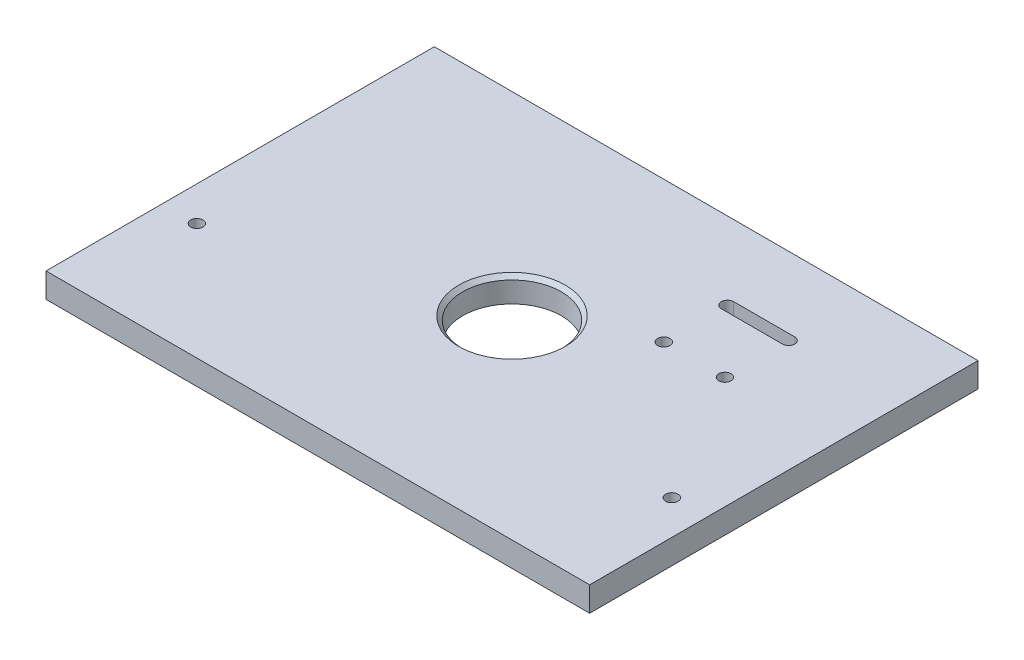
SolidWorks part; units mm, degrees
material "Oak"
ref_plane "Front Plane" through (0, 0, 0) normal (0, 0, 1) x (1, 0, 0)
ref_plane "Top Plane" through (0, 0, 0) normal (0, 1, 0) x (1, 0, 0)
ref_plane "Right Plane" through (0, 0, 0) normal (1, 0, 0) x (0, 0, -1)
sketch "Sketch1" plane through (0, 0, 0) normal (0, 1, 0) x (1, 0, 0)
  line L1 (0, 0) -> (140, 0)
  line L2 (0, 0) -> (0, 100)
  line L3 (0, 100) -> (140, 100)
  line L4 (140, 0) -> (140, 100)
  dimension "D1" = 140
  dimension "D2" = 100
extrude "Boss-Extrude1" add sketch "Sketch1" along normal blind 6.35
sketch "Sketch2" plane through (0, 6.35, 0) normal (0, 1, 0) x (1, 0, 0)
  line L0 (70, 100) -> (70, 0) construction
  line L1 (140, 100) -> (0, 100) construction
  line L2 (0, 0) -> (140, 0) construction
  line L3 (0, 50) -> (140, 50) construction
  line L4 (0, 100) -> (0, 0) construction
  line L5 (140, 0) -> (140, 100) construction
  circle A0 centre (70, 50) radius 12.705
  dimension "D1" = 25.41
extrude "Cut-Extrude1" cut sketch "Sketch2" against normal blind 10
sketch "Sketch3" plane through (0, 6.35, 0) normal (0, 1, 0) x (1, 0, 0)
  line L1 (140, 0) -> (140, 100) construction
  line L2 (0, 0) -> (140, 0) construction
  circle A0 centre (8.85, 30) radius 1.5875
  circle A1 centre (131.15, 30) radius 1.5875
  point P0 (0, 100)
  point P1 (0, 30)
  point P3 (8.85, 30)
  point P6 (131.15, 30)
  dimension "D1" = 3.175
  dimension "D2" = 3.175
  dimension "D3" = 8.85
  dimension "D4" = 8.85
  dimension "D6" = 30
extrude "Cut-Extrude2" cut sketch "Sketch3" against normal blind 10
chamfer "Chamfer1" distance 1 angle 45 1 edges at (70, 6.35, -37.295)
sketch "Sketch4" plane through (0, 6.35, 0) normal (0, 1, 0) x (1, 0, 0)
  line L0 (95.4, 81.6925) -> (111.13, 81.6925)
  line L1 (95.4, 78.5175) -> (111.13, 78.5175)
  circle A0 centre (95.4, 63.705) radius 1.5875
  circle A1 centre (111.13, 63.705) radius 1.5875
  circle A2 centre (111.13, 80.105) radius 1.5875
  circle A3 centre (95.4, 80.105) radius 1.5875
  circle A4 centre (70, 50) radius 13.705 construction
  point P9 (70, 63.705)
  dimension "D1" = 3.175
  dimension "D2" = 3.175
  dimension "D3" = 3.175
  dimension "D4" = 3.175
  dimension "D5" = 15.73
  dimension "D6" = 16.4
  dimension "D7" = 25.4
extrude "Cut-Extrude4" cut sketch "Sketch4" against normal blind 10 contours A3 L1 A2 L0 | A3 | A1 | A2 | A0 region at (103.265, 6.35, -80.105) region at (95.4, 6.35, -80.105) region at (111.13, 6.35, -63.705)
